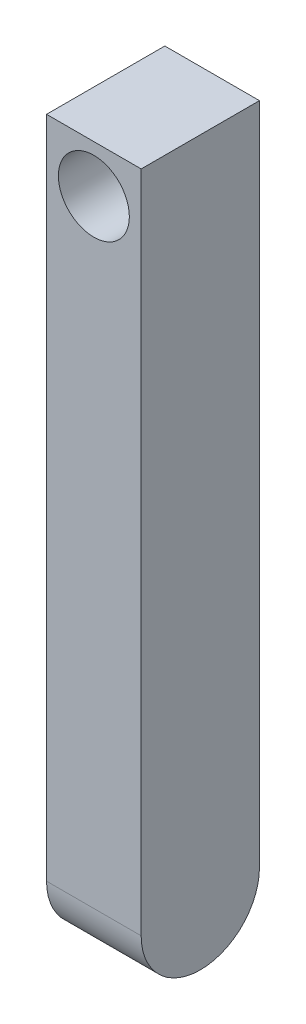
SolidWorks part; units mm, degrees
ref_plane "Front Plane" through (0, 0, 0) normal (0, 0, 1) x (1, 0, 0)
ref_plane "Top Plane" through (0, 0, 0) normal (0, 1, 0) x (1, 0, 0)
ref_plane "Right Plane" through (0, 0, 0) normal (1, 0, 0) x (0, 0, -1)
sketch "Sketch1" plane through (0, 0, 0) normal (0, 0, 1) x (1, 0, 0)
  line L1 (-37.6696, 540.4704) -> (42.3304, 540.4704)
  line L2 (-37.6696, 540.4704) -> (-37.6696, -71.0296)
  line L3 (-37.6696, -71.0296) -> (42.3304, -71.0296)
  line L4 (42.3304, 540.4704) -> (42.3304, -71.0296)
  circle A0 centre (2.3304, 500.4704) radius 30
  dimension "D1" = 60
  dimension "D2" = 40
  dimension "D3" = 40
  dimension "D4" = 40
  dimension "D5" = 571.5
extrude "Boss-Extrude1" add sketch "Sketch1" along normal blind 100
fillet "Fillet2" radius 50 2 edges at (2.3304, -71.0296, 0) (2.3304, -71.0296, 100)
